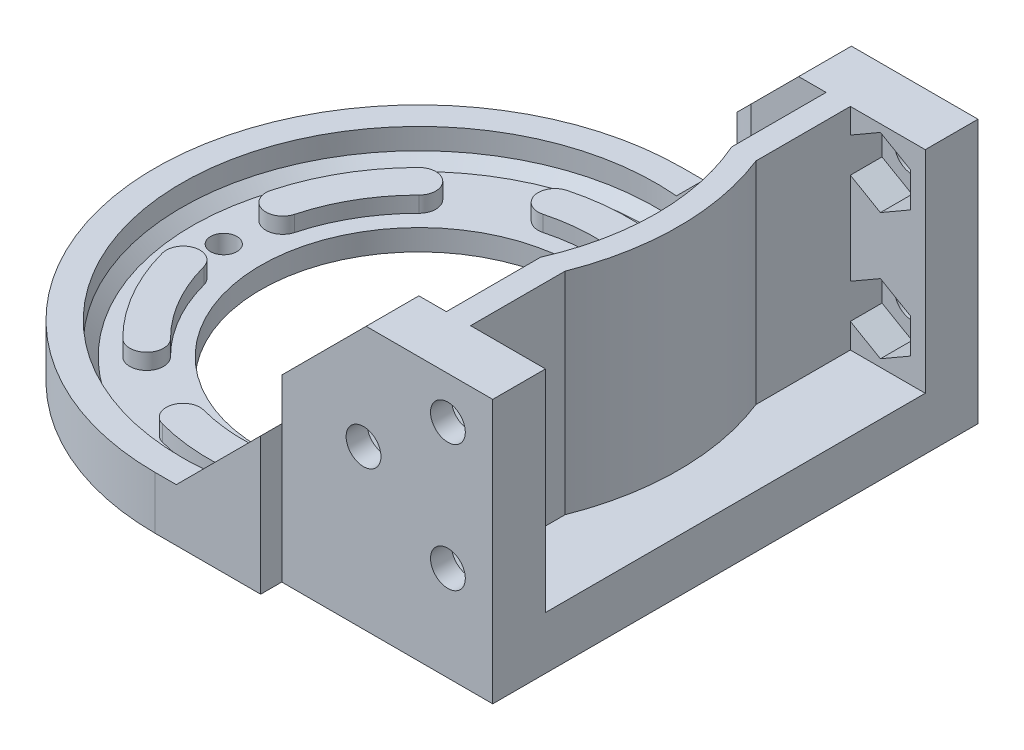
SolidWorks part; units mm, degrees
ref_plane "前视基准面" through (0, 0, 0) normal (0, 0, 1) x (1, 0, 0)
ref_plane "上视基准面" through (0, 0, 0) normal (0, 1, 0) x (1, 0, 0)
ref_plane "右视基准面" through (0, 0, 0) normal (1, 0, 0) x (0, 0, -1)
sketch "草图1" plane through (0, 0, 0) normal (0, 1, 0) x (1, 0, 0)
  circle A0 centre (0, 0) radius 25
  dimension "D1" = 50
extrude "凸台-拉伸1" add sketch "草图1" along normal blind 5
sketch "草图2" plane through (0, 5, 0) normal (0, 1, 0) x (1, 0, 0)
  circle A0 centre (0, 0) radius 15
  dimension "D1" = 30
extrude "切除-拉伸1" cut sketch "草图2" against normal up to next
sketch "草图3" plane through (0, 5, 0) normal (0, 1, 0) x (1, 0, 0)
  circle A0 centre (0, 0) radius 22.5
  dimension "D1" = 45
extrude "切除-拉伸2" cut sketch "草图3" against normal offset from surface (3 mm away) 2 up to face at (0, 0, 15)
sketch "草图4" plane through (0, 2, 0) normal (0, 1, 0) x (1, 0, 0)
  line L0 (0, 0) -> (-18.5, 0) construction
  line L1 (0, 0) -> (9.25, 16.0215) construction
  line L2 (0, 0) -> (9.25, -16.0215) construction
  circle A0 centre (0, 0) radius 18.5 construction
  circle A1 centre (9.25, -16.0215) radius 1.25
  circle A2 centre (-18.5, 0) radius 1.25
  circle A3 centre (9.25, 16.0215) radius 1.25
  dimension "D1" = 37
  dimension "D4" = 2.5
  dimension "D2" = 120
  dimension "D3" = 120
extrude "切除-拉伸3" cut sketch "草图4" against normal up to next
chamfer "倒角1" distance 1 angle 45 1 edges at (0, 2, 22.5)
sketch "草图7" plane through (0, 2, 0) normal (0, 1, 0) x (1, 0, 0)
  line L0 (-9.125, -15.805) -> (0, 0) construction
  line L1 (0, 0) -> (-15.805, -9.125) construction
  line L2 (0, 0) -> (-15.805, 9.125) construction
  line L3 (0, 0) -> (0, 18.25) construction
  line L4 (0, 0) -> (15.805, 9.125) construction
  line L5 (0, 0) -> (15.805, -9.125) construction
  line L6 (0, 0) -> (0, -18.25) construction
  line L7 (-17.6281, 4.7234) -> (0, 0) construction
  circle A0 centre (0, 0) radius 18.25 construction
  arc A1 (4.7234, 17.6281) -> (-4.7234, 17.6281) centre (0, 0) ccw construction
  arc A2 (5.1376, 19.1736) -> (-5.1376, 19.1736) centre (0, 0) ccw
  arc A3 (4.3093, 16.0827) -> (-4.3093, 16.0827) centre (0, 0) ccw
  arc A4 (4.3093, 16.0827) -> (5.1376, 19.1736) centre (4.7234, 17.6281) ccw
  arc A5 (-5.1376, 19.1736) -> (-4.3093, 16.0827) centre (-4.7234, 17.6281) ccw
  arc A6 (12.9047, 12.9047) -> (17.6281, 4.7234) centre (0, 0) cw construction
  arc A7 (19.1736, 5.1376) -> (14.0361, 14.0361) centre (0, 0) ccw
  arc A8 (16.0827, 4.3093) -> (11.7733, 11.7733) centre (0, 0) ccw
  arc A9 (16.0827, 4.3093) -> (19.1736, 5.1376) centre (17.6281, 4.7234) ccw
  arc A10 (14.0361, 14.0361) -> (11.7733, 11.7733) centre (12.9047, 12.9047) ccw
  arc A11 (17.6281, -4.7234) -> (12.9047, -12.9047) centre (0, 0) cw construction
  arc A12 (14.0361, -14.0361) -> (19.1736, -5.1376) centre (0, 0) ccw
  arc A13 (11.7733, -11.7733) -> (16.0827, -4.3093) centre (0, 0) ccw
  arc A14 (11.7733, -11.7733) -> (14.0361, -14.0361) centre (12.9047, -12.9047) ccw
  arc A15 (19.1736, -5.1376) -> (16.0827, -4.3093) centre (17.6281, -4.7234) ccw
  arc A16 (4.7234, -17.6281) -> (-4.7234, -17.6281) centre (0, 0) cw construction
  arc A17 (-5.1376, -19.1736) -> (5.1376, -19.1736) centre (0, 0) ccw
  arc A18 (-4.3093, -16.0827) -> (4.3093, -16.0827) centre (0, 0) ccw
  arc A19 (-4.3093, -16.0827) -> (-5.1376, -19.1736) centre (-4.7234, -17.6281) ccw
  arc A20 (5.1376, -19.1736) -> (4.3093, -16.0827) centre (4.7234, -17.6281) ccw
  arc A21 (-12.9047, -12.9047) -> (-17.6281, -4.7234) centre (0, 0) cw construction
  arc A22 (-19.1736, -5.1376) -> (-14.0361, -14.0361) centre (0, 0) ccw
  arc A23 (-16.0827, -4.3093) -> (-11.7733, -11.7733) centre (0, 0) ccw
  arc A24 (-16.0827, -4.3093) -> (-19.1736, -5.1376) centre (-17.6281, -4.7234) ccw
  arc A25 (-14.0361, -14.0361) -> (-11.7733, -11.7733) centre (-12.9047, -12.9047) ccw
  arc A26 (-17.6281, 4.7234) -> (-12.9047, 12.9047) centre (0, 0) cw construction
  arc A27 (-14.0361, 14.0361) -> (-19.1736, 5.1376) centre (0, 0) ccw
  arc A28 (-11.7733, 11.7733) -> (-16.0827, 4.3093) centre (0, 0) ccw
  arc A29 (-11.7733, 11.7733) -> (-14.0361, 14.0361) centre (-12.9047, 12.9047) ccw
  arc A30 (-19.1736, 5.1376) -> (-16.0827, 4.3093) centre (-17.6281, 4.7234) ccw
  point P6 (0, 18.25)
  point P11 (15.805, 9.125)
  point P19 (15.805, -9.125)
  point P27 (0, -18.25)
  point P35 (-15.805, -9.125)
  point P43 (-15.805, 9.125)
  dimension "D1" = 36.5
  dimension "D9" = 1.6
  dimension "D2" = 30
  dimension "D3" = 60
  dimension "D4" = 60
  dimension "D5" = 60
  dimension "D6" = 60
  dimension "D7" = 30
  dimension "D8" = 15
extrude "凸台-拉伸2" add sketch "草图7" along normal blind 1.5
sketch "草图8" plane through (0, 0, 0) normal (0, 1, 0) x (1, 0, 0)
  line L0 (0, 25) -> (30, 25)
  line L1 (30, 25) -> (30, -25)
  line L2 (30, -25) -> (0, -25)
  circle A0 centre (0, 0) radius 25 construction
  arc A1 (0, 25) -> (0, -25) centre (0, 0) cw
  dimension "D1" = 30
extrude "凸台-拉伸3" add sketch "草图8" along normal up to surface (5 mm away) up to face at (0, 5, 22.5)
sketch "草图10" plane through (0, 5, 0) normal (0, 1, 0) x (1, 0, 0)
  line L0 (30, 25) -> (10, 25)
  line L1 (30, 25) -> (0, 25) construction
  line L2 (10, 25) -> (10, 23)
  line L3 (10, 23) -> (30, 23)
  line L4 (30, -25) -> (30, 25) construction
  line L5 (30, 23) -> (30, 25)
  dimension "D1" = 2
  dimension "D2" = 20
extrude "切除-拉伸4" cut sketch "草图10" against normal up to next
sketch "草图9" plane through (0, 5, 0) normal (0, 1, 0) x (1, 0, 0)
  line L0 (13.5, 18) -> (30, 18)
  line L1 (30, -25) -> (30, 23) construction
  line L2 (30, 18) -> (30, 23)
  line L3 (30, 23) -> (10, 23)
  line L4 (10, 23) -> (10, 20.1556)
  line L5 (10, 25) -> (0, 25) construction
  line L6 (10, 25) -> (10, 23) construction
  circle A0 centre (0, 0) radius 22.5 construction
  arc A1 (10, 20.1556) -> (13.5, 18) centre (0, 0) cw
  dimension "D1" = 2
  dimension "D2" = 5
extrude "凸台-拉伸4" add sketch "草图9" along normal blind 20
sketch "草图11" plane through (0, 0, -18) normal (0, 0, 1) x (1, 0, 0)
  line L0 (21.75, 25) -> (21.75, 5) construction
  line L1 (13.5, 25) -> (30, 25) construction
  line L2 (0, 5) -> (30, 5) construction
  line L5 (17.75, 9) -> (25.75, 9) construction
  line L6 (17.75, 9) -> (17.75, 21) construction
  line L7 (17.75, 21) -> (25.75, 21) construction
  line L8 (25.75, 9) -> (25.75, 21) construction
  line L9 (17.75, 9) -> (25.75, 21) construction
  line L10 (17.75, 21) -> (25.75, 9) construction
  circle A0 centre (17.75, 15) radius 1.65
  circle A1 centre (25.75, 21) radius 1.65
  circle A2 centre (25.75, 9) radius 1.65
  point P6 (21.75, 15)
  dimension "D3" = 3.3
  dimension "D1" = 8
  dimension "D2" = 12
extrude "切除-拉伸5" cut sketch "草图11" against normal up to next and the other way through all
sketch "草图12" plane through (0, 0, -18) normal (0, 0, 1) x (1, 0, 0)
  line L1 (28.6, 22.6454) -> (25.75, 24.2909)
  line L2 (25.75, 24.2909) -> (22.9, 22.6454)
  line L3 (22.9, 22.6454) -> (22.9, 19.3546)
  line L4 (22.9, 19.3546) -> (25.75, 17.7091)
  line L5 (25.75, 17.7091) -> (28.6, 19.3546)
  line L6 (28.6, 19.3546) -> (28.6, 22.6454)
  line L7 (28.6, 10.6454) -> (25.75, 12.2909)
  line L8 (25.75, 12.2909) -> (22.9, 10.6454)
  line L9 (22.9, 10.6454) -> (22.9, 7.3546)
  line L10 (22.9, 7.3546) -> (25.75, 5.7091)
  line L11 (25.75, 5.7091) -> (28.6, 7.3546)
  line L12 (28.6, 7.3546) -> (28.6, 10.6454)
  line L13 (20.6, 16.6454) -> (17.75, 18.2909)
  line L14 (17.75, 18.2909) -> (14.9, 16.6454)
  line L15 (14.9, 16.6454) -> (14.9, 13.3546)
  line L16 (14.9, 13.3546) -> (17.75, 11.7091)
  line L17 (17.75, 11.7091) -> (20.6, 13.3546)
  line L18 (20.6, 13.3546) -> (20.6, 16.6454)
  circle A0 centre (25.75, 21) radius 2.85 construction
  circle A1 centre (25.75, 9) radius 2.85 construction
  circle A2 centre (17.75, 15) radius 2.85 construction
  dimension "D1" = 5.7
  dimension "D2" = 5.7
  dimension "D3" = 5.7
extrude "切除-拉伸6" cut sketch "草图12" against normal blind 3
chamfer "倒角4" distance 8 angle 45 2 edges at (10, 5, -21.5778) (10, 25, -21.5778)
sketch "草图17" plane through (0, 0, -23) normal (0, 0, -1) x (-1, 0, 0)
  line L0 (-10, 13) -> (-10, 5)
  line L1 (-10, 5) -> (-2, 5)
  line L3 (-2, 5) -> (-10, 13)
extrude "凸台-拉伸8" add sketch "草图17" along normal blind 2
mirror "镜向3" about plane through (0, 0, 0) normal (0, 0, 1) of "切除-拉伸4", "切除-拉伸6", "切除-拉伸5", "倒角4", "凸台-拉伸4", "凸台-拉伸8"
sketch "草图15" plane through (0, 0, -18) normal (0, 0, 1) x (1, 0, 0)
  line L0 (18, 25) -> (30, 25) construction
  line L1 (20.6, 25) -> (22.9, 25)
  line L2 (20.6, 25) -> (20.6, 5)
  line L3 (20.6, 5) -> (22.9, 5)
  line L4 (22.9, 25) -> (22.9, 5)
  line L5 (13.5, 5) -> (30, 5) construction
  line L6 (20.6, 13.3546) -> (20.6, 16.6454) construction
  line L7 (22.9, 10.6454) -> (22.9, 7.3546) construction
extrude "凸台-拉伸9" add sketch "草图15" along normal up to surface (36 mm away) up to face at (25.75, 9, 18)
sketch "草图14" plane through (0, 25, 0) normal (0, 1, 0) x (1, 0, 0)
  circle A0 centre (0, 0) radius 22.5
  circle A1 centre (0, 0) radius 22.5 construction
extrude "切除-拉伸8" cut sketch "草图14" against normal up to next
sketch "草图16" plane through (0, 5, 0) normal (0, 1, 0) x (1, 0, 0)
  line L0 (20.6, 9.0493) -> (22.9, 9.0493) construction
  line L1 (22.9, -18) -> (22.9, 18) construction
  line L2 (22.9, 9.0493) -> (22.9, -9.0493)
  circle A0 centre (0, 0) radius 24.6232 construction
  arc A1 (22.9, -9.0493) -> (22.9, 9.0493) centre (0, 0) ccw
extrude "凸台-拉伸7" add sketch "草图16" along normal up to surface (20 mm away) up to face at (23.0071, 25, 0)
sketch "草图18" plane through (0, 5, 0) normal (0, 1, 0) x (1, 0, 0)
  line L0 (13.5, 18) -> (20.6, 18) construction
  line L2 (20.6, 9.0493) -> (20.6, 18) construction
  line L3 (22.9, 14) -> (30, 14) construction
  line L11 (30, -18) -> (30, 18) construction
  line L12 (30, 0) -> (24.6232, 0) construction
  line L13 (22.9, 18) -> (30, 18) construction
  line L15 (22.9, 9.0493) -> (22.9, 18) construction
  line L16 (22.9, 9.0493) -> (22.9, 18) construction
  circle A1 centre (18.6, 16) radius 1.35
  arc A2 (22.9, -9.0493) -> (22.9, 9.0493) centre (0, 0) ccw construction
  circle A3 centre (25.75, 14) radius 1.35
  circle A4 centre (27.3116, 0) radius 1.35 construction
  dimension "D1" = 2.7
  dimension "D2" = 2
  dimension "D3" = 2
  dimension "D4" = 4
  dimension "D5" = 2.85
extrude "切除-拉伸9" [suppressed] cut sketch "草图18" against normal up to next
sketch "草图20" [suppressed] plane through (0, 5, 0) normal (0, 1, 0) x (1, 0, 0)
  line L1 (28.6, 12.3546) -> (28.6, 15.6454)
  line L2 (28.6, 15.6454) -> (25.75, 17.2909)
  line L3 (25.75, 17.2909) -> (22.9, 15.6454)
  line L4 (22.9, 15.6454) -> (22.9, 12.3546)
  line L5 (22.9, 12.3546) -> (25.75, 10.7091)
  line L6 (25.75, 10.7091) -> (28.6, 12.3546)
  circle A0 centre (25.75, 14) radius 2.85 construction
  dimension "D1" = 5.7
extrude "切除-拉伸10" [suppressed] cut sketch "草图20" against normal blind 3
mirror "镜向4" [suppressed] about plane through (0, 0, 0) normal (0, 0, 1)
sketch "草图19" [suppressed] plane through (0, 5, 0) normal (0, 1, 0) x (1, 0, 0)
  line L1 (26.45, 10.2338) -> (29.3, 11.8792)
  line L2 (29.3, 11.8792) -> (29.3, 15.1701)
  line L3 (29.3, 15.1701) -> (26.45, 16.8156)
  line L4 (26.45, 16.8156) -> (23.6, 15.1701)
  line L5 (23.6, 15.1701) -> (23.6, 11.8792)
  line L6 (23.6, 11.8792) -> (26.45, 10.2338)
  circle A0 centre (26.45, 13.5247) radius 2.85 construction
  dimension "D1" = 5.7
